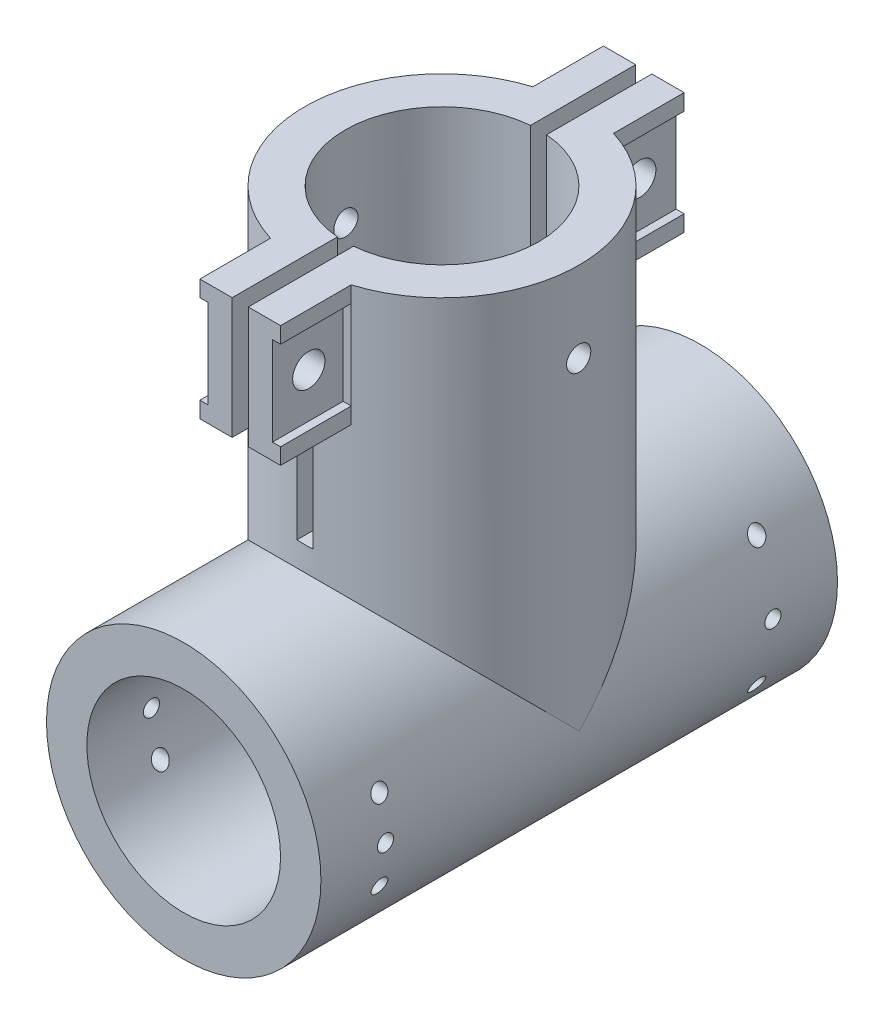
SolidWorks part; units mm, degrees
ref_plane "Ön Düzlem" through (0, 0, 0) normal (0, 0, 1) x (1, 0, 0)
ref_plane "Üst Düzlem" through (0, 0, 0) normal (0, 1, 0) x (1, 0, 0)
ref_plane "Sağ Düzlem" through (0, 0, 0) normal (1, 0, 0) x (0, 0, -1)
sketch "Çizim1" plane through (0, 0, 0) normal (0, 0, 1) x (1, 0, 0)
  circle A0 centre (-32.2971, 4.4232) radius 17
  circle A1 centre (-32.2971, 4.4232) radius 12
  dimension "D1" = 34
  dimension "D2" = 5
extrude "Yükseklik-Ekstrüzyon1" add sketch "Çizim1" along normal blind 64
ref_axis "Eksen2" through (-32.2971, 4.4232, 64) along (0, 0, -1)
ref_plane "Düzlem1" through (0, 4.4232, 0) normal (0, 1, 0) x (1, 0, 0)
sketch "Çizim2" plane through (0, 4.4232, 0) normal (0, 1, 0) x (1, 0, 0)
  line L0 (-32.2971, -64) -> (-32.2971, 0) construction
  line L1 (-15.2971, 0) -> (-49.2971, 0) construction
  circle A0 centre (-32.2971, -32) radius 17
  circle A1 centre (-32.2971, -32) radius 12
  dimension "D1" = 32
  dimension "D2" = 5
  dimension "D3" = 34
extrude "Yükseklik-Ekstrüzyon2" add sketch "Çizim2" along normal blind 50
sketch "Çizim3" plane through (0, 0, 64) normal (0, 0, 1) x (1, 0, 0)
  circle A0 centre (-32.2971, 4.4232) radius 12
extrude "Kes-Ekstrüzyon2" cut sketch "Çizim3" against normal through all
sketch "Çizim4" plane through (0, 54.4232, 0) normal (0, 1, 0) x (1, 0, 0)
  circle A0 centre (-32.2971, -32) radius 12
ref_axis "Eksen3" through (-32.2971, 54.4232, 32) along (0, -1, 0)
ref_plane "Düzlem2" through (0, 0, 32) normal (0, 0, -1) x (-1, 0, 0)
sketch "Çizim6" plane through (0, 0, 32) normal (0, 0, -1) x (-1, 0, 0)
  line L0 (49.2971, 54.4232) -> (15.2971, 54.4232) construction
  line L1 (37.2971, 54.4232) -> (27.2971, 54.4232)
  line L2 (37.2971, 54.4232) -> (37.2971, 39.4232)
  line L3 (37.2971, 39.4232) -> (27.2971, 39.4232)
  line L4 (27.2971, 54.4232) -> (27.2971, 39.4232)
  line L5 (32.2971, 54.4232) -> (32.2971, 15.582) construction
  dimension "D1" = 10
  dimension "D2" = 5
  dimension "D3" = 15
extrude "Yükseklik-Ekstrüzyon3" add sketch "Çizim6" along normal mid plane 50
sketch "Çizim7" plane through (0, 0, 57) normal (0, 0, 1) x (1, 0, 0)
  line L0 (-37.2971, 54.4232) -> (-27.2971, 54.4232) construction
  line L1 (-33.2971, 54.4232) -> (-31.2971, 54.4232)
  line L2 (-33.2971, 54.4232) -> (-33.2971, 24.4232)
  line L3 (-33.2971, 24.4232) -> (-31.2971, 24.4232)
  line L4 (-31.2971, 54.4232) -> (-31.2971, 24.4232)
  line L5 (-32.2971, 54.4232) -> (-32.2971, 15.582) construction
  dimension "D1" = 2
  dimension "D2" = 1
  dimension "D3" = 30
extrude "Kes-Ekstrüzyon5" cut sketch "Çizim7" against normal blind 50
extrude "Kes-Ekstrüzyon6" cut sketch "Çizim4" against normal blind 50
sketch "Çizim8" plane through (-27.2971, 0, 0) normal (1, 0, 0) x (0, 0, -1)
  line L0 (-57, 54.4232) -> (-57, 39.4232) construction
  line L1 (-57, 52.4232) -> (-48.2481, 52.4232)
  line L2 (-57, 52.4232) -> (-57, 41.4232)
  line L3 (-57, 41.4232) -> (-48.2481, 41.4232)
  line L4 (-48.2481, 52.4232) -> (-48.2481, 41.4232)
  line L5 (-48.2481, 39.4232) -> (-48.2481, 54.4232) construction
  line L6 (-15.7519, 54.4232) -> (-15.7519, 39.4232) construction
  line L7 (-15.7519, 52.4232) -> (-7, 52.4232)
  line L8 (-15.7519, 52.4232) -> (-15.7519, 41.4232)
  line L9 (-15.7519, 41.4232) -> (-7, 41.4232)
  line L10 (-7, 52.4232) -> (-7, 41.4232)
  line L11 (-7, 54.4232) -> (-7, 39.4232) construction
  line L12 (-48.2481, 54.4232) -> (-57, 54.4232) construction
  line L13 (-48.2481, 39.4232) -> (-57, 39.4232) construction
  line L14 (-7, 54.4232) -> (-15.7519, 54.4232) construction
  line L15 (-7, 39.4232) -> (-15.7519, 39.4232) construction
  dimension "D1" = 2
  dimension "D2" = 2
  dimension "D3" = 2
  dimension "D4" = 2
extrude "Kes-Ekstrüzyon7" cut sketch "Çizim8" against normal blind 1
sketch "Çizim9" plane through (-28.2971, 0, 0) normal (1, 0, 0) x (0, 0, -1)
  line L0 (-7, 54.4232) -> (-15.7519, 54.4232) construction
  line L1 (-57, 52.4232) -> (-57, 41.4232) construction
  line L4 (-7, 41.4232) -> (-7, 52.4232) construction
  line L5 (-43.9583, 54.4232) -> (-57, 54.4232) construction
  circle A0 centre (-52.5, 46.9232) radius 2
  circle A1 centre (-11.5, 46.9232) radius 2
  point P6 (-57, 46.9232)
  dimension "D1" = 4
  dimension "D2" = 4
  dimension "D3" = 4.5
  dimension "D4" = 4.5
  dimension "D5" = 7.5
  dimension "D6" = 7.5
extrude "Kes-Ekstrüzyon8" cut sketch "Çizim9" against normal through all
ref_plane "Düzlem3" through (-15.2971, 0, 0) normal (1, 0, 0) x (0, 0, -1)
sketch "Çizim10" plane through (-15.2971, 0, 0) normal (1, 0, 0) x (0, 0, -1)
  line L0 (35.2, 4.4232) -> (-35.2, 4.4232) construction
  line L1 (-64, 4.4232) -> (0, 4.4232) construction
  line L2 (-64, 21.4232) -> (-64, -12.5768) construction
  line L3 (0, -12.5768) -> (0, 21.4232) construction
  line L4 (-32, -27.5) -> (-32, 27.5) construction
  line L5 (-15.7519, 54.4232) -> (-48.2481, 54.4232) construction
  circle A0 centre (-56, 4.4232) radius 1
  circle A1 centre (-56, 9.4232) radius 1
  circle A2 centre (-56, -0.5768) radius 1
  circle A3 centre (-8, 4.4232) radius 1
  circle A4 centre (-8, 12.4232) radius 1
  circle A5 centre (-8, -3.5768) radius 1
  circle A6 centre (-32, 44.4232) radius 1.5
  dimension "D1" = 2
  dimension "D2" = 2
  dimension "D3" = 2
  dimension "D4" = 2
  dimension "D5" = 2
  dimension "D6" = 2
  dimension "D7" = 5
  dimension "D8" = 5
  dimension "D9" = 8
  dimension "D10" = 8
  dimension "D11" = 8
  dimension "D13" = 8
  dimension "D14" = 3
  dimension "D15" = 10
  dimension "D12" = 8
extrude "Kes-Ekstrüzyon9" cut sketch "Çizim10" against normal through all
sketch "Çizim11" plane through (-37.2971, 0, 0) normal (-1, 0, 0) x (0, 0, 1)
  line L0 (15.7519, 51.4232) -> (9.7679, 51.4232)
  line L1 (15.7519, 39.4232) -> (15.7519, 54.4232) construction
  line L2 (7, 39.4232) -> (7, 54.4232) construction
  line L3 (7, 51.4232) -> (7, 42.4232)
  line L4 (9.7679, 42.4232) -> (15.7519, 42.4232)
  line L5 (9.7679, 49.9232) -> (9.7679, 51.4232)
  line L6 (14.9641, 44.9232) -> (14.9641, 48.9232)
  line L7 (14.9641, 48.9232) -> (11.5, 50.9232)
  line L8 (11.5, 50.9232) -> (9.7679, 49.9232)
  line L9 (15.7519, 52.4232) -> (15.7519, 51.4232)
  line L10 (9.7679, 43.9232) -> (11.5, 42.9232)
  line L11 (11.5, 42.9232) -> (14.9641, 44.9232)
  line L12 (9.7679, 43.9232) -> (9.7679, 42.4232)
  line L13 (15.7519, 41.4232) -> (7, 41.4232)
  line L14 (15.7519, 52.4232) -> (7, 52.4232)
  line L15 (7, 54.4232) -> (15.7519, 54.4232) construction
  line L16 (7, 39.4232) -> (15.7519, 39.4232) construction
  line L17 (7, 42.4232) -> (7, 41.4232)
  line L18 (7, 52.4232) -> (7, 51.4232)
  line L19 (8.0359, 46.9232) -> (8.0359, 44.9232) [skipped]
  line L20 (15.7519, 42.4232) -> (15.7519, 41.4232)
  line L24 (48.2481, 42.4232) -> (48.2481, 41.4232)
  line L25 (57, 52.4232) -> (57, 51.4232)
  line L26 (57, 42.4232) -> (57, 41.4232)
  line L27 (48.2481, 52.4232) -> (57, 52.4232)
  line L28 (48.2481, 41.4232) -> (57, 41.4232)
  line L29 (54.2321, 43.9232) -> (54.2321, 42.4232)
  line L30 (52.5, 42.9232) -> (49.0359, 44.9232)
  line L31 (54.2321, 43.9232) -> (52.5, 42.9232)
  line L32 (48.2481, 52.4232) -> (48.2481, 51.4232)
  line L33 (52.5, 50.9232) -> (54.2321, 49.9232)
  line L34 (49.0359, 48.9232) -> (52.5, 50.9232)
  line L35 (49.0359, 44.9232) -> (49.0359, 48.9232)
  line L36 (54.2321, 49.9232) -> (54.2321, 51.4232)
  line L37 (54.2321, 42.4232) -> (48.2481, 42.4232)
  line L38 (57, 51.4232) -> (57, 42.4232)
  line L39 (48.2481, 51.4232) -> (54.2321, 51.4232)
  circle A0 centre (11.5, 46.9232) radius 3.4641 construction
  circle A1 centre (52.5, 46.9232) radius 3.4641 construction
  dimension "D1" = 4
  dimension "D2" = 180
  dimension "D3" = 2
  dimension "D4" = 1
  dimension "D5" = 2
  dimension "D6" = 1
extrude "Kes-Ekstrüzyon10" cut sketch "Çizim11" against normal blind 1
